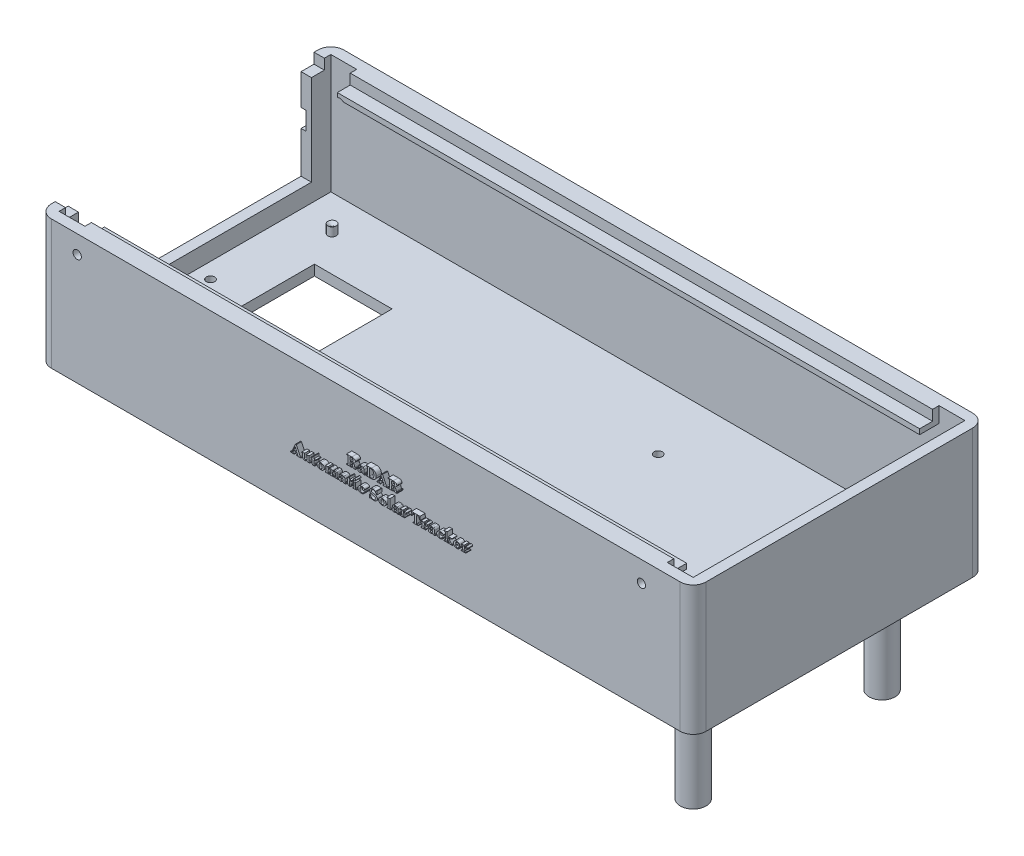
SolidWorks part; units mm, degrees
other "Markup1"
sketch "Sketch11" plane through (-122.5, 50, -52.5) normal (-0.0618, 0.9884, -0.1386) x (-0.9911, -0.0444, 0.1256)
ref_plane "Front Plane" through (0, 0, 0) normal (0, 0, 1) x (1, 0, 0)
ref_plane "Top Plane" through (0, 0, 0) normal (0, 1, 0) x (1, 0, 0)
ref_plane "Right Plane" through (0, 0, 0) normal (1, 0, 0) x (0, 0, -1)
sketch "Sketch1" plane through (0, 0, 0) normal (0, 1, 0) x (1, 0, 0)
  line L7 (126.5, -56.5) -> (-126.5, -56.5)
  line L8 (126.5, -56.5) -> (126.5, 56.5)
  line L9 (126.5, 56.5) -> (-126.5, 56.5)
  line L10 (-126.5, -56.5) -> (-126.5, 56.5)
  line L11 (126.5, -56.5) -> (-126.5, 56.5) construction
  line L12 (126.5, 56.5) -> (-126.5, -56.5) construction
  point P0 (0, 0)
  point P6 (0, 0)
  dimension "D3" = 113
  dimension "D4" = 253
extrude "Boss-Extrude2" add sketch "Sketch1" along normal blind 50 contours L10 L9 L8 L7
sketch "Sketch4" plane through (0, 50, 0) normal (0, 1, 0) x (1, 0, 0)
  line L1 (122.5, -52.5) -> (-122.5, -52.5)
  line L2 (122.5, -52.5) -> (122.5, 52.5)
  line L3 (122.5, 52.5) -> (-122.5, 52.5)
  line L4 (-122.5, -52.5) -> (-122.5, 52.5)
  line L5 (122.5, -52.5) -> (-122.5, 52.5) construction
  line L6 (122.5, 52.5) -> (-122.5, -52.5) construction
  point P0 (0, 0)
  dimension "D1" = 105
  dimension "D2" = 245
extrude "Cut-Extrude1" cut sketch "Sketch4" against normal blind 46
sketch "Sketch7" plane through (0, 4, 0) normal (0, 1, 0) x (1, 0, 0)
  circle A0 centre (-108.31, -37.92) radius 1.6
  circle A1 centre (-108.31, 38.79) radius 1.6
  circle A2 centre (108.31, 38.79) radius 1.6
  circle A3 centre (108.31, -37.92) radius 1.6
  dimension "D1" = 3.2
  dimension "D2" = 108.31
  dimension "D5" = 108.31
  dimension "D3" = 76.71
  dimension "D4" = 76.71
  dimension "D6" = 37.92
  dimension "D7" = 216.62
  dimension "D8" = 115.0466
extrude "Boss-Extrude4" add sketch "Sketch7" along normal blind 8.4
hole_wizard "CSK for M3 Countersunk Flat Head Screw1" positions "Sketch14" profile "Sketch15" countersink size "M3" standard "ISO"
sketch "Sketch14" plane through (0, 12.4, 0) normal (0, 1, 0) x (1, 0, 0)
  circle A2 centre (-108.31, -37.92) radius 1.6 construction
  point P0 (-108.31, 38.79)
  point P3 (108.31, 38.79)
  point P6 (108.31, -37.92)
  point P9 (-108.31, -37.92)
sketch "Sketch15" plane through (-108.31, 12.4, -38.79) normal (1, 0, 0) x (0, 0, 1)
  line L0 (0, 0) -> (0, 6)
  line L1 (0, 6) -> (1.7, 4.9785)
  line L2 (1.7, 4.9785) -> (1.7, 1.45)
  line L3 (1.7, 1.45) -> (3.15, 0)
  line L5 (3.15, 0) -> (0, 0)
  line L6 (-1.7, 1.45) -> (-3.15, 0) construction
  line L10 (0, 6) -> (-1.7, 4.9785) construction
  line L11 (0, -6.35) -> (0, 107.95) construction
  dimension "Hole Dia." = 3.4
  dimension "Hole Depth" = 6
  dimension "Near C'Sink Dia." = 6.3
  dimension "Near C'Sink Angle" = 90
  dimension "Drill Angle" = 118
sketch "Sketch27" plane through (0, 0, 56.5) normal (0, 0, 1) x (1, 0, 0)
  line L0 (126.5, 50) -> (-126.5, 50) construction
  line L1 (-112.5, 50) -> (112.5, 50)
  line L2 (-112.5, 50) -> (-112.5, 44)
  line L3 (-112.5, 44) -> (112.5, 44)
  line L4 (112.5, 50) -> (112.5, 44)
  point P6 (0, 44)
  dimension "D1" = 6
  dimension "D2" = 225
extrude "Boss-Extrude8" add sketch "Sketch27" against normal up to surface (109 mm away) up to face at (0, 27, -52.5)
sketch "Sketch28" plane through (-126.5, 0, 0) normal (-1, 0, 0) x (0, 0, 1)
  line L0 (-50, 50) -> (-50, 46)
  line L1 (56.5, 50) -> (-56.5, 50) construction
  line L2 (-50, 46) -> (-45, 46)
  line L3 (-45, 46) -> (-45, 44)
  line L4 (-45, 44) -> (45, 44)
  line L5 (45, 44) -> (45, 46)
  line L6 (45, 46) -> (50, 46)
  line L7 (50, 46) -> (50, 50)
  line L8 (50, 50) -> (-50, 50)
  point P4 (0, 44)
  point P11 (0, 50)
  dimension "D1" = 90
  dimension "D2" = 100
  dimension "D3" = 4
  dimension "D4" = 2
  dimension "D5" = 4
  dimension "D6" = 2
extrude "Cut-Extrude2" cut sketch "Sketch28" against normal up to surface (249 mm away) up to face at (122.5, 27, 0)
fillet "Fillet1" radius 5 4 edges at (126.5, 25, 56.5) (126.5, 25, -56.5) (-126.5, 25, 56.5) (-126.5, 25, -56.5)
sketch "Sketch31" plane through (-126.5, 0, 0) normal (-1, 0, 0) x (0, 0, 1)
  line L1 (-45, 44) -> (45, 44)
  line L2 (-45, 44) -> (-45, 11)
  line L3 (-45, 11) -> (45, 11)
  line L4 (45, 44) -> (45, 11)
  dimension "D1" = 33
extrude "Cut-Extrude3" cut sketch "Sketch31" against normal blind 5 contours L2 L3 L4 L1
sketch "Sketch32" plane through (0, 4, 0) normal (0, 1, 0) x (1, 0, 0)
  circle A0 centre (-116.5, 0) radius 1.6
  circle A1 centre (28.5, 28) radius 1.6
  circle A2 centre (28.5, -28) radius 1.6
extrude "Boss-Extrude9" add sketch "Sketch32" along normal blind 2
sketch "Sketch33" plane through (0, 0, 0) normal (0, -1, 0) x (1, 0, 0)
  circle A0 centre (-116.5, 0) radius 1.6
  circle A1 centre (28.5, 28) radius 1.6
  circle A2 centre (28.5, -28) radius 1.6
  dimension "D1" = 3.2
  dimension "D2" = 3.2
  dimension "D3" = 3.2
hole_wizard "CSK for M3 Hex Socket Countersunk Cap Screw1" positions "Sketch36" profile "Sketch37" countersink size "M3" standard "ISO"
sketch "Sketch36" plane through (0, 6, 0) normal (0, 1, 0) x (1, 0, 0)
  point P0 (-116.5, 0)
  point P3 (28.5, 28)
  point P6 (28.5, -28)
sketch "Sketch37" plane through (-116.5, 6, 0) normal (1, 0, 0) x (0, 0, 1)
  line L0 (0, 0) -> (0, 8.2)
  line L1 (0, 8.2) -> (1.6, 7.2386)
  line L2 (1.6, 7.2386) -> (1.6, 1.76)
  line L3 (1.6, 1.76) -> (3.36, 0)
  line L5 (3.36, 0) -> (0, 0)
  line L6 (-1.6, 1.76) -> (-3.36, 0) construction
  line L10 (0, 8.2) -> (-1.6, 7.2386) construction
  line L11 (0, -6.35) -> (0, 107.95) construction
  dimension "Hole Dia." = 3.2
  dimension "Hole Depth" = 8.2
  dimension "Near C'Sink Dia." = 6.72
  dimension "Near C'Sink Angle" = 90
  dimension "Drill Angle" = 118
sketch "Sketch38" plane through (0, 0, 0) normal (0, -1, 0) x (1, 0, 0)
  line L0 (38.5, 32.827) -> (-126.5, 32.827) construction
  line L1 (-101.5, 24.827) -> (-71.5, 24.827)
  line L2 (-101.5, 24.827) -> (-101.5, -25.173)
  line L3 (-101.5, -25.173) -> (-71.5, -25.173)
  line L4 (-71.5, 24.827) -> (-71.5, -25.173)
  line L6 (-121.5, 33) -> (-121.5, 5) construction
  dimension "D1" = 30
  dimension "D2" = 50
  dimension "D3" = 8
  dimension "D4" = 20
extrude "Cut-Extrude6" cut sketch "Sketch38" against normal blind 4 contours L2 L3 L4 L1
sketch "Sketch39" plane through (0, 0, 56.5) normal (0, 0, 1) x (1, 0, 0)
  text T0 "<b>              RaDAR </b>\r\n<b>Automatic Solar Tracker</b>" font "Century Schoolbook" height 3.5
extrude "Boss-Extrude10" add sketch "Sketch39" along normal blind 2
sketch "Sketch40" plane through (-126.5, 0, 0) normal (-1, 0, 0) x (0, 0, 1)
  line L0 (-45, 46) -> (-45, 11) construction
  line L1 (-45, 34) -> (-52, 34)
  line L2 (-45, 34) -> (-45, 27)
  line L3 (-45, 27) -> (-52, 27)
  line L4 (-52, 34) -> (-52, 27)
  line L5 (-50, 46) -> (-45, 46) construction
  line L6 (45, 11) -> (45, 46) construction
  line L7 (45, 34) -> (52, 34)
  line L8 (45, 34) -> (45, 27)
  line L9 (45, 27) -> (52, 27)
  line L10 (52, 34) -> (52, 27)
  line L11 (45, 46) -> (50, 46) construction
  circle A0 centre (-48.5, 30.5) radius 1.6
  circle A1 centre (48.5, 30.5) radius 1.6
  dimension "D4" = 3.2
  dimension "D5" = 3.5
  dimension "D6" = 3.5
  dimension "D10" = 3.2
  dimension "D11" = 3.5
  dimension "D12" = 3.5
  dimension "D1" = 7
  dimension "D2" = 7
  dimension "D3" = 12
  dimension "D7" = 7
  dimension "D8" = 7
  dimension "D9" = 12
extrude "Cut-Extrude7" cut sketch "Sketch40" against normal blind 2
sketch "Sketch43" plane through (0, 0, 56.5) normal (0, 0, 1) x (1, 0, 0)
  line L1 (-121.5, 50) -> (-121.5, 0) construction
  line L4 (121.5, 50) -> (-121.5, 50) construction
  circle A0 centre (-111.5, 43) radius 1.6
  dimension "D1" = 10
  dimension "D2" = 7
hole_wizard "Ø3.0 (3) Diameter Hole3" positions "Sketch44" profile "Sketch45" hole size "Ø3.0" standard "ISO"
sketch "Sketch44" plane through (0, 0, 56.5) normal (0, 0, 1) x (1, 0, 0)
  point P0 (-111.5, 43)
sketch "Sketch45" plane through (-111.5, 43, 56.5) normal (1, 0, 0) x (0, -1, 0)
  line L0 (0, 0) -> (0, 6)
  line L1 (0, 6) -> (1.5, 5.0987)
  line L2 (1.5, 5.0987) -> (1.5, 0.025)
  line L3 (1.5, 0.025) -> (1.525, 0)
  line L5 (1.525, 0) -> (0, 0)
  line L6 (-1.5, 0.025) -> (-1.525, 0) construction
  line L10 (0, 6) -> (-1.5, 5.0987) construction
  line L11 (0, -6.35) -> (0, 107.95) construction
  dimension "Hole Dia." = 3
  dimension "Hole Depth" = 6
  dimension "Near C'Sink Dia." = 3.05
  dimension "Near C'Sink Angle" = 90
  dimension "Drill Angle" = 118
sketch "Sketch46" plane through (0, 0, 0) normal (0, -1, 0) x (1, 0, 0)
  line L0 (121.5, 56.5) -> (-121.5, 56.5) construction
  line L2 (126.5, 51.5) -> (126.5, -51.5) construction
  line L3 (121.5, -56.5) -> (-121.5, -56.5) construction
  circle A0 centre (106.5, 36.5) radius 5
  circle A1 centre (106.5, -36.5) radius 5
  dimension "D1" = 10
  dimension "D2" = 20
  dimension "D4" = 10
  dimension "D5" = 20
  dimension "D6" = 20
  dimension "D3" = 20
extrude "Boss-Extrude11" add sketch "Sketch46" along normal blind 40
extrude "Cut-Extrude8" cut sketch "Sketch43" against normal through all contours A0
sketch "Sketch52" plane through (0, 0, -56.5) normal (0, 0, -1) x (-1, 0, 0)
  line L0 (-121.5, 50) -> (121.5, 50) construction
  line L1 (-121.5, 50) -> (-121.5, 0) construction
  circle A0 centre (-106.5, 42) radius 1.6
  dimension "D1" = 3.2
  dimension "D2" = 8
  dimension "D3" = 15
extrude "Cut-Extrude9" cut sketch "Sketch52" against normal through all
